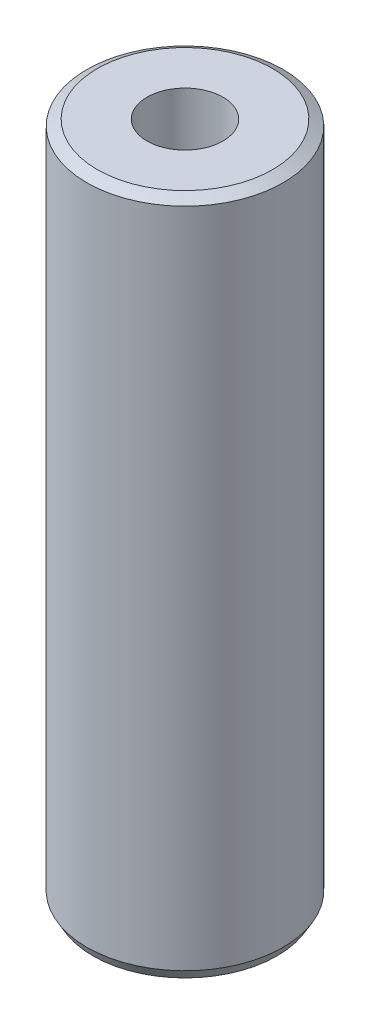
SolidWorks part; units mm, degrees
ref_plane "Front Plane" through (0, 0, 0) normal (0, 0, 1) x (1, 0, 0)
ref_plane "Top Plane" through (0, 0, 0) normal (0, 1, 0) x (1, 0, 0)
ref_plane "Right Plane" through (0, 0, 0) normal (1, 0, 0) x (0, 0, -1)
sketch "Sketch1" plane through (0, 0, 0) normal (0, 1, 0) x (1, 0, 0)
  circle A0 centre (0, 0) radius 40
  dimension "SHAFT_OD" = 80
extrude "Boss-Extrude1" add sketch "Sketch1" along normal blind 276.6132
sketch "Sketch2" plane through (0, 0, 0) normal (0, 1, 0) x (1, 0, 0)
  circle A0 centre (0, 0) radius 15.4938
  dimension "BORE_D" = 30.9876
extrude "Cut-Extrude1" cut sketch "Sketch2" along normal through all
chamfer "Chamfer1" distance 2.4792 angle 60 2 edges at (0, 276.6132, 40) (0, 0, 40) first distance on face at (0, 276.6132, 40) first distance on face at (0, 0, 15.4938)
